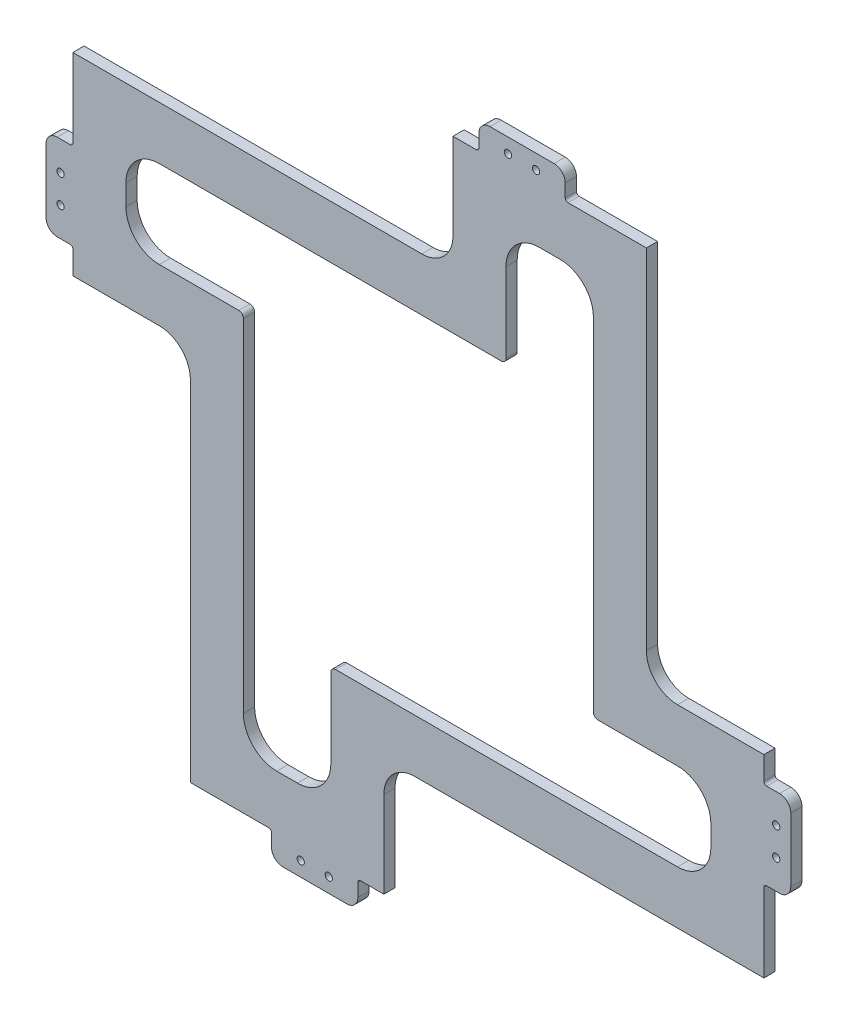
SolidWorks part; units mm, degrees
ref_plane "front" through (0, 0, 0) normal (0, 0, 1) x (1, 0, 0)
ref_plane "top" through (0, 0, 0) normal (0, 1, 0) x (1, 0, 0)
ref_plane "right" through (0, 0, 0) normal (1, 0, 0) x (0, 0, -1)
ref_axis "Axis1" through (0, 0, -69.7337) along (0, 0, 1)
sketch "Sketch1" plane through (0, 0, 0) normal (0, 0, 1) x (1, 0, 0)
  line L0 (-7.8359, 7.8359) -> (7.8359, 7.8359)
  line L1 (7.8359, 7.8359) -> (7.8359, -7.8359)
  line L2 (7.8359, -7.8359) -> (-7.8359, -7.8359)
  line L3 (-7.8359, -7.8359) -> (-7.8359, 7.8359)
  line L4 (-7.8359, 0) -> (-89.5647, 0) construction
  line L5 (-89.5647, 0) -> (0, 15.7927)
  line L6 (-89.5647, 0) -> (0, 7.8359)
  dimension "D1" = 10
  dimension "D2" = 5
  dimension "D3" = 89.5647
  dimension "D4" = 90.9464
  dimension "A" = 15.6718
sketch "Sketch2" plane through (0, 0, 0) normal (0, 0, 1) x (1, 0, 0)
  line L0 (-6.2687, 7.8359) -> (3.7612, 7.8359)
  line L1 (-7.8359, 7.8359) -> (7.8359, 7.8359) construction
  line L2 (4.0747, 8.1493) -> (4.0747, 11.7538)
  line L3 (7.8359, 11.7538) -> (7.8359, 3.1344)
  line L4 (7.8359, 3.1344) -> (10.3434, 3.1344)
  line L5 (10.3434, 3.1344) -> (10.3434, 15.6718)
  line L6 (2.6156, 15.6718) -> (1.5672, 15.6718)
  line L7 (1.5672, 11.7538) -> (4.0747, 11.7538) construction
  line L8 (1.5672, 15.6718) -> (1.5672, 11.7538)
  line L10 (10.3434, 15.6718) -> (6.7875, 15.6718)
  line L11 (6.6605, 15.7988) -> (6.6605, 16.383)
  line L12 (6.1525, 16.891) -> (3.2506, 16.891)
  line L13 (2.7426, 16.383) -> (2.7426, 15.7988)
  line L14 (0.1567, 10.3434) -> (-6.2687, 10.3434)
  line L15 (-6.2687, 10.3434) -> (-6.2687, 7.8359)
  line L16 (7.8359, 7.8359) -> (7.8359, -7.8359) construction
  line L18 (5.4851, 13.1643) -> (6.4254, 13.1643)
  arc A0 (1.5672, 11.7538) -> (0.1567, 10.3434) centre (0.1567, 11.7538) cw
  arc A1 (3.2506, 16.891) -> (2.7426, 16.383) centre (3.2506, 16.383) ccw
  arc A2 (6.6605, 16.383) -> (6.1525, 16.891) centre (6.1525, 16.383) ccw
  arc A3 (2.7426, 15.7988) -> (2.6156, 15.6718) centre (2.6156, 15.7988) cw
  circle A4 centre (4.0665, 16.2306) radius 0.1651
  arc A5 (6.7875, 15.6718) -> (6.6605, 15.7988) centre (6.7875, 15.7988) cw
  circle A6 centre (5.3365, 16.2306) radius 0.1651
  arc A9 (6.4254, 13.1643) -> (7.8359, 11.7538) centre (6.4254, 11.7538) cw
  arc A10 (4.0747, 11.7538) -> (5.4851, 13.1643) centre (5.4851, 11.7538) cw
  arc A11 (3.7612, 7.8359) -> (4.0747, 8.1493) centre (3.7612, 8.1493) ccw
  point P16 (4.7015, 16.891)
  dimension "D9" = 0.3134
  dimension "D6" = 0.127
  dimension "D14" = 0.3302
  dimension "D2" = 7.8359
  dimension "D5" = 3.9179
  dimension "D8" = 2.5075
  dimension "D10" = 2.5075
  dimension "D12" = 6.2687
  dimension "D13" = 3.1344
  dimension "D4" = 1.5672
  dimension "D15" = 8.7762
  dimension "D11" = 4.7015
  dimension "D16" = 0.635
  dimension "D17" = 0.635
  dimension "D18" = 0.5588
  dimension "D19" = 3.918
extrude "Extrude1" add sketch "Sketch2" against normal mid plane 0.508
pattern_circular "CirPattern1" count 4 over 360 about axis through (0, 0, -69.7337) along (0, 0, 1) of "Extrude1"
sketch "Sketch7" plane through (0, 0, 0.254) normal (0, 0, 1) x (1, 0, 0)
  line L168 (-11.7539, 3.9731) -> (-8.1493, 3.9731)
  line L169 (-13.2659, 6.4254) -> (-13.2659, 5.4851)
  line L170 (-7.9375, 3.7612) -> (-7.9375, -11.7539)
  line L171 (-6.4254, -13.2659) -> (-5.4851, -13.2659)
  line L172 (-3.9731, -11.7539) -> (-3.9731, -8.1493)
  line L173 (-3.7612, -7.9375) -> (11.7539, -7.9375)
  line L174 (13.2659, -6.4254) -> (13.2659, -5.4851)
  line L175 (11.7539, -3.9731) -> (8.1493, -3.9731)
  line L176 (3.7612, 7.9375) -> (-11.7539, 7.9375)
  line L177 (7.9375, -3.7612) -> (7.9375, 11.7538)
  line L178 (3.9731, 11.7538) -> (3.9731, 8.1493)
  line L179 (6.4254, 13.2659) -> (5.4851, 13.2659)
  line L180 (-11.7539, 3.9731) -> (-8.1493, 3.9731)
  line L181 (-13.2659, 6.4254) -> (-13.2659, 5.4851)
  line L182 (-7.9375, 3.7612) -> (-7.9375, -11.7539)
  line L183 (-6.4254, -13.2659) -> (-5.4851, -13.2659)
  line L184 (-3.9731, -11.7539) -> (-3.9731, -8.1493)
  line L185 (-3.7612, -7.9375) -> (11.7539, -7.9375)
  line L186 (13.2659, -6.4254) -> (13.2659, -5.4851)
  line L187 (11.7539, -3.9731) -> (8.1493, -3.9731)
  line L188 (3.7612, 7.9375) -> (-11.7539, 7.9375)
  line L189 (7.9375, -3.7612) -> (7.9375, 11.7538)
  line L190 (3.9731, 11.7538) -> (3.9731, 8.1493)
  line L191 (6.4254, 13.2659) -> (5.4851, 13.2659)
  arc A156 (-7.9375, 3.7612) -> (-8.1493, 3.9731) centre (-8.1493, 3.7612) ccw
  arc A157 (-13.2659, 5.4851) -> (-11.7539, 3.9731) centre (-11.7539, 5.4851) ccw
  arc A158 (-11.7539, 7.9375) -> (-13.2659, 6.4254) centre (-11.7539, 6.4254) ccw
  arc A159 (-7.9375, -11.7539) -> (-6.4254, -13.2659) centre (-6.4254, -11.7539) ccw
  arc A160 (-5.4851, -13.2659) -> (-3.9731, -11.7539) centre (-5.4851, -11.7539) ccw
  arc A161 (-3.7612, -7.9375) -> (-3.9731, -8.1493) centre (-3.7612, -8.1493) ccw
  arc A162 (11.7539, -7.9375) -> (13.2659, -6.4254) centre (11.7539, -6.4254) ccw
  arc A163 (13.2659, -5.4851) -> (11.7539, -3.9731) centre (11.7539, -5.4851) ccw
  arc A164 (7.9375, -3.7612) -> (8.1493, -3.9731) centre (8.1493, -3.7612) ccw
  arc A165 (3.7612, 7.9375) -> (3.9731, 8.1493) centre (3.7612, 8.1493) ccw
  arc A166 (7.9375, 11.7538) -> (6.4254, 13.2659) centre (6.4254, 11.7538) ccw
  arc A167 (5.4851, 13.2659) -> (3.9731, 11.7538) centre (5.4851, 11.7538) ccw
  arc A168 (-7.9375, 3.7612) -> (-8.1493, 3.9731) centre (-8.1493, 3.7612) ccw
  arc A169 (-13.2659, 5.4851) -> (-11.7539, 3.9731) centre (-11.7539, 5.4851) ccw
  arc A170 (-11.7539, 7.9375) -> (-13.2659, 6.4254) centre (-11.7539, 6.4254) ccw
  arc A171 (-7.9375, -11.7539) -> (-6.4254, -13.2659) centre (-6.4254, -11.7539) ccw
  arc A172 (-5.4851, -13.2659) -> (-3.9731, -11.7539) centre (-5.4851, -11.7539) ccw
  arc A173 (-3.7612, -7.9375) -> (-3.9731, -8.1493) centre (-3.7612, -8.1493) ccw
  arc A174 (11.7539, -7.9375) -> (13.2659, -6.4254) centre (11.7539, -6.4254) ccw
  arc A175 (13.2659, -5.4851) -> (11.7539, -3.9731) centre (11.7539, -5.4851) ccw
  arc A176 (7.9375, -3.7612) -> (8.1493, -3.9731) centre (8.1493, -3.7612) ccw
  arc A177 (3.7612, 7.9375) -> (3.9731, 8.1493) centre (3.7612, 8.1493) ccw
  arc A178 (7.9375, 11.7538) -> (6.4254, 13.2659) centre (6.4254, 11.7538) ccw
  arc A179 (5.4851, 13.2659) -> (3.9731, 11.7538) centre (5.4851, 11.7538) ccw
  dimension "D1" = 0.1016
extrude "Cut-Extrude3" cut sketch "Sketch7" against normal blind 0.635
equation "\"D2@Sketch2\" = .5 * \"A\""
equation "\"D13@Sketch2\" = .2 * \"A\""
equation "\"D8@Sketch2\" = .16 * \"A\""
equation "\"D10@Sketch2\" = .16 * \"A\""
equation "\"D5@Sketch2\" = .25 * \"A\""
equation "\"D12@Sketch2\" = .4 * \"A\""
equation "\"D4@Sketch2\"=.1*\"A\""
equation "\"D9@Sketch2\"=.02*\"A\""
equation "\"D11@Sketch2\"=.3*\"A\""
